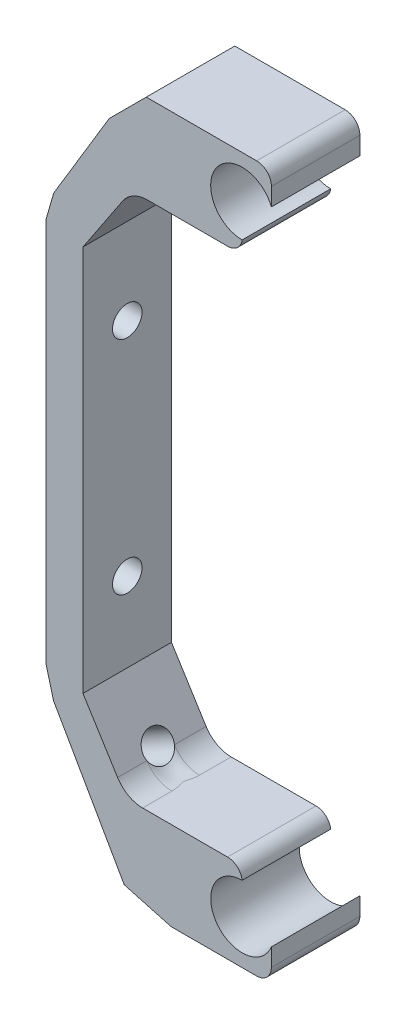
SolidWorks part; units mm, degrees
ref_plane "前视基准面" through (0, 0, 0) normal (0, 0, 1) x (1, 0, 0)
ref_plane "上视基准面" through (0, 0, 0) normal (0, 1, 0) x (1, 0, 0)
ref_plane "右视基准面" through (0, 0, 0) normal (1, 0, 0) x (0, 0, -1)
sketch "草图1" plane through (0, 0, 0) normal (0, 0, 1) x (1, 0, 0)
  line L0 (6.0052, 13.1888) -> (-4.7864, 9.6578) construction
  line L1 (13.5052, 16.1888) -> (-1.4948, 16.1888) construction
  line L2 (13.5052, 16.1888) -> (13.5052, 10.1888) construction
  line L3 (13.5052, 10.1888) -> (-1.4948, 10.1888) construction
  line L9 (-1.4948, 16.1888) -> (-1.4948, 10.1888) construction
  line L10 (13.5052, 16.1888) -> (-1.4948, 10.1888) construction
  line L14 (13.5052, 10.1888) -> (-1.4948, 16.1888) construction
  line L15 (13.5052, -25.6712) -> (-1.4948, -25.6712) construction
  line L20 (13.5052, -25.6712) -> (13.5052, -31.6712) construction
  line L21 (13.5052, -31.6712) -> (-1.4948, -31.6712) construction
  line L22 (6.0052, 13.1888) -> (6.0052, -28.6712) construction
  line L23 (-1.4948, -25.6712) -> (-1.4948, -31.6712) construction
  line L24 (13.5052, -25.6712) -> (-1.4948, -31.6712) construction
  line L25 (13.5052, -31.6712) -> (-1.4948, -25.6712) construction
  line L26 (-4.7864, 9.6578) -> (-4.7864, -24.9643) construction
  line L27 (-4.7864, -24.9643) -> (6.0052, -28.6712) construction
  line L38 (7.0606, -32.979) -> (7.0606, -20.5309) construction
  line L43 (-1.4948, 10.1888) -> (-4.7864, 5.246)
  line L44 (-4.7864, -20.9675) -> (-1.8508, -25.6712)
  line L45 (-1.4948, -31.6712) -> (-7.2864, -21.5062)
  line L46 (-7.2864, -21.5062) -> (-7.2864, 6.5622)
  line L47 (-7.2864, 6.5622) -> (-1.4948, 16.1888)
  line L49 (-4.7864, -20.9675) -> (-4.7864, 5.246)
  line L70 (-1.4948, 10.1888) -> (6.0052, 10.1888)
  line L71 (6.0052, 10.1888) -> (6.0052, 11.054)
  line L72 (7.9873, 13.9817) -> (7.9873, 16.1888)
  line L73 (7.9873, 16.1888) -> (-1.4948, 16.1888)
  line L74 (-1.8508, -25.6712) -> (6.0052, -25.6712)
  line L75 (6.0052, -25.6712) -> (6.0052, -26.5412)
  line L76 (7.9829, -29.4623) -> (7.9829, -31.6712)
  line L77 (7.9829, -31.6712) -> (-1.4948, -31.6712)
  circle A2 centre (6.0052, -28.6712) radius 2.13 construction
  circle A3 centre (6.0052, 13.1888) radius 2.1348 construction
  arc A6 (6.0052, 11.054) -> (7.9873, 13.9817) centre (6.0052, 13.1888) cw
  arc A7 (6.0052, -26.5412) -> (7.9829, -29.4623) centre (6.0052, -28.6712) ccw
  point P19 (0, 0)
  dimension "D1" = 41.86
  dimension "D2" = 6
  dimension "D6" = 2.1348
  dimension "D7" = 2.13
  dimension "D3" = 6
  dimension "D4" = 15
  dimension "D5" = 15
extrude "凸台-拉伸2" add sketch "草图1" along normal blind 6
sketch "草图2" plane through (-7.2864, 0, 0) normal (-1, 0, 0) x (0, 0, 1)
  line L0 (2.9973, -0.5798) -> (2.9973, -15.5798) construction
  line L1 (3, 5.4645) -> (3, 3.6208) construction
  circle A0 centre (2.9973, -0.5798) radius 1
  circle A1 centre (2.9973, -15.5798) radius 1
extrude "切除-拉伸1" cut sketch "草图2" against normal blind 3
sketch "草图3" plane through (-8.2487, 4.9627, 0) normal (-0.8569, 0.5155, 0) x (0, 0, 1)
  circle A0 centre (2.9334, 6.7018) radius 1
extrude "切除-拉伸2" cut sketch "草图3" against normal through all
sketch "草图4" plane through (-14.7512, -8.4047, 0) normal (-0.8689, -0.495, 0) x (0, 0, 1)
  circle A0 centre (3.0828, -19.923) radius 1
extrude "切除-拉伸3" cut sketch "草图4" against normal through all
chamfer "倒角1" distance 1 angle 45 2 edges at (-1.4948, 16.1888, 3) (-1.4948, -31.6712, 3)
chamfer "倒角2" distance 1 angle 15 2 edges at (-7.2864, -21.5062, 3) (-7.2864, 6.5622, 3)
fillet "圆角1" radius 2 2 edges at (-1.4948, 10.1888, 3) (-1.8508, -25.6712, 3)
fillet "圆角2" radius 1 4 edges at (7.9829, -31.6712, 3) (6.0052, -25.6712, 3) (6.0052, 10.1888, 3) (7.9873, 16.1888, 3)
